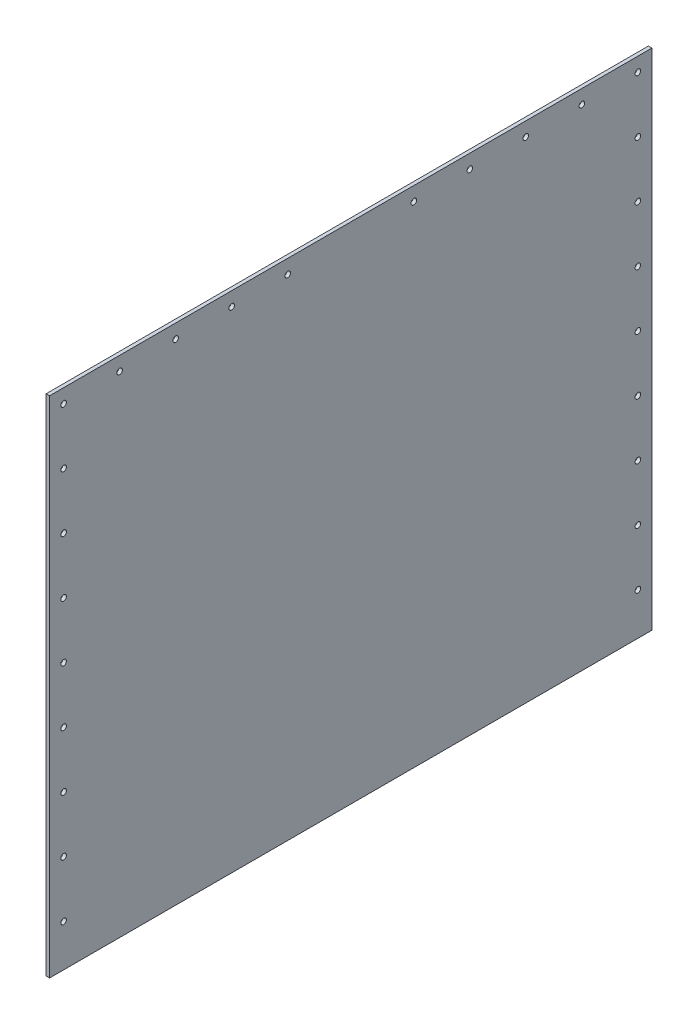
SolidWorks part; units mm, degrees
ref_plane "Front Plane" through (0, 0, 0) normal (0, 0, 1) x (1, 0, 0)
ref_plane "Top Plane" through (0, 0, 0) normal (0, 1, 0) x (1, 0, 0)
ref_plane "Right Plane" through (0, 0, 0) normal (1, 0, 0) x (0, 0, -1)
sketch "Sketch1" plane through (0, 0, 0) normal (1, 0, 0) x (0, 0, -1)
  line L0 (0, 0) -> (0, 457.2)
  line L1 (0, 457.2) -> (546.1, 457.2)
  line L3 (546.1, 457.2) -> (546.1, 0)
  line L4 (546.1, 0) -> (0, 0)
  dimension "D1" = 546.1
  dimension "D4" = 457.2
extrude "Boss-Extrude1" add sketch "Sketch1" along normal blind 3.175
sketch "Sketch2" plane through (3.175, 0, 0) normal (1, 0, 0) x (0, 0, -1)
  line L2 (0, 0) -> (546.1, 0) construction
  line L3 (273.05, 457.2) -> (273.05, 0) construction
  line L4 (546.1, 457.2) -> (0, 457.2) construction
  line L5 (0, 457.2) -> (0, 0) construction
  circle A96 centre (12.7, 444.5) radius 2.54
  circle A97 centre (63.5, 444.5) radius 2.54
  circle A98 centre (114.3, 444.5) radius 2.54
  circle A99 centre (165.1, 444.5) radius 2.54
  circle A100 centre (215.9, 444.5) radius 2.54
  circle A101 centre (12.7, 393.7) radius 2.54
  circle A102 centre (12.7, 342.9) radius 2.54
  circle A103 centre (12.7, 292.1) radius 2.54
  circle A104 centre (12.7, 241.3) radius 2.54
  circle A105 centre (12.7, 190.5) radius 2.54
  circle A106 centre (12.7, 139.7) radius 2.54
  circle A107 centre (12.7, 88.9) radius 2.54
  circle A108 centre (12.7, 38.1) radius 2.54
  circle A109 centre (533.4, 38.1) radius 2.54
  circle A110 centre (533.4, 88.9) radius 2.54
  circle A111 centre (533.4, 139.7) radius 2.54
  circle A112 centre (533.4, 190.5) radius 2.54
  circle A113 centre (533.4, 241.3) radius 2.54
  circle A114 centre (533.4, 292.1) radius 2.54
  circle A115 centre (533.4, 342.9) radius 2.54
  circle A116 centre (533.4, 393.7) radius 2.54
  circle A117 centre (330.2, 444.5) radius 2.54
  circle A118 centre (381, 444.5) radius 2.54
  circle A119 centre (431.8, 444.5) radius 2.54
  circle A120 centre (482.6, 444.5) radius 2.54
  circle A121 centre (533.4, 444.5) radius 2.54
  dimension "D1" = 5.08
  dimension "D2" = 12.7
  dimension "D3" = 12.7
extrude "Cut-Extrude1" cut sketch "Sketch2" against normal through all
